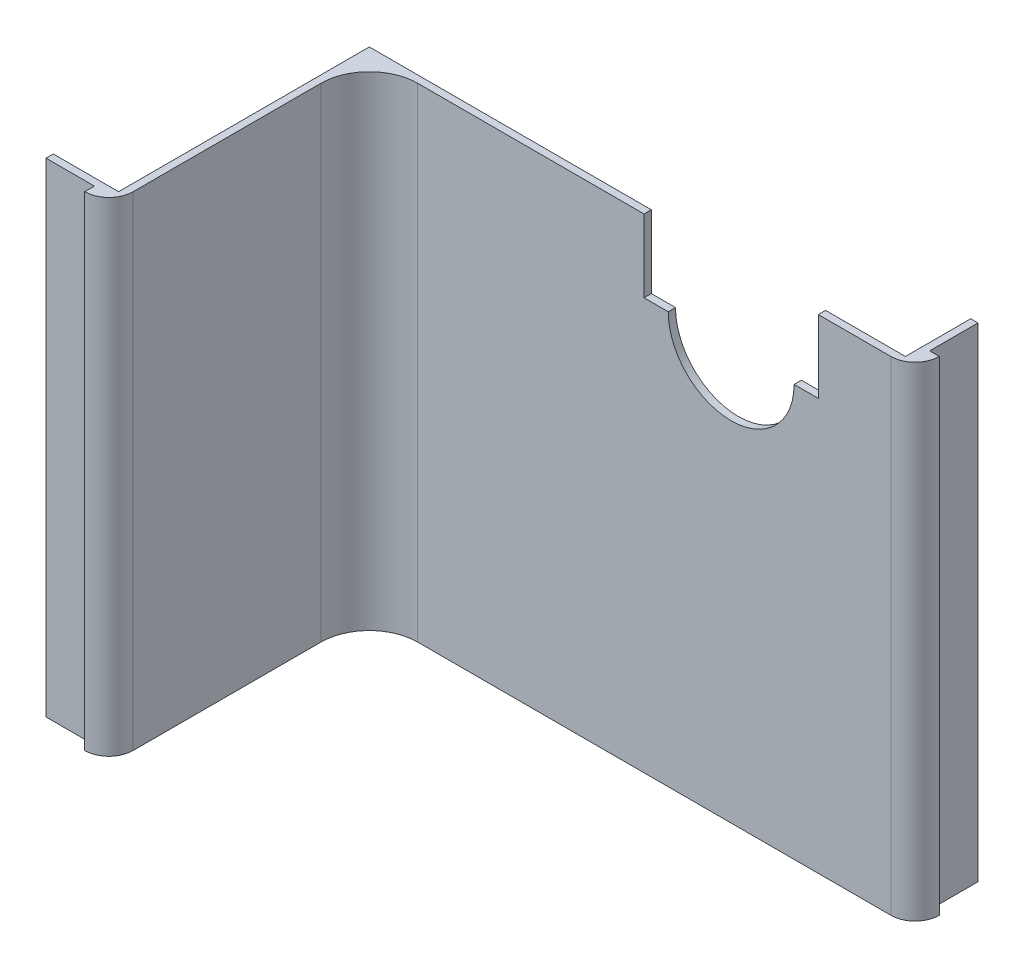
SolidWorks part; units mm, degrees
material "ABS"
ref_plane "Спереди" through (0, 0, 0) normal (0, 0, 1) x (1, 0, 0)
ref_plane "Сверху" through (0, 0, 0) normal (0, 1, 0) x (1, 0, 0)
ref_plane "Справа" through (0, 0, 0) normal (1, 0, 0) x (0, 0, -1)
sketch "Эскиз1" plane through (0, 0, 0) normal (0, 1, 0) x (1, 0, 0)
  line L0 (0, 0) -> (-97.768, 0)
  line L1 (-107.768, -10) -> (-107.768, -48.8)
  line L2 (-112.768, -53.8) -> (-112.768, -51.8)
  line L3 (-112.768, -51.8) -> (-122.768, -51.8)
  line L4 (5, 5) -> (3, 5)
  line L5 (3, 5) -> (3, 15)
  line L6 (3, 15) -> (1.5, 15)
  line L7 (0, 0) -> (0, 1.5) construction
  line L8 (1.5, 15) -> (1.5, 1.5)
  line L9 (-107.768, -48.8) -> (-109.268, -48.8) construction
  line L10 (-122.768, -51.8) -> (-122.768, -50.3)
  line L11 (-122.768, -50.3) -> (-109.268, -50.3)
  line L12 (-109.268, -50.3) -> (-109.268, 1.5)
  line L13 (-109.268, 1.5) -> (1.5, 1.5)
  arc A0 (-97.768, 0) -> (-107.768, -10) centre (-97.768, -10) ccw
  arc A1 (-107.768, -48.8) -> (-112.768, -53.8) centre (-112.768, -48.8) cw
  arc A2 (0, 0) -> (5, 5) centre (0, 5) ccw
  dimension "D1" = 97.768
  dimension "D2" = 5
  dimension "D6" = 10
  dimension "D9" = 5
  dimension "D3" = 2
  dimension "D4" = 1.5
  dimension "D5" = 1.5
  dimension "D7" = 1.5
  dimension "D8" = 38.8
  dimension "D10" = 2
  dimension "D11" = 1.5
  dimension "D12" = 10
  dimension "D13" = 10
extrude "Бобышка-Вытянуть1" add sketch "Эскиз1" along normal blind 100
sketch "Эскиз4" plane through (0, 0, 0) normal (0, 0, 1) x (1, 0, 0)
  line L8 (-51, 85) -> (-15, 85) construction
  line L11 (5, 50) -> (-55.9199, 50) construction
  line L12 (5, 100) -> (-15, 100) construction
  line L13 (-15, 85) -> (-20, 85)
  line L14 (-15, 100) -> (-15, 85)
  line L15 (-51, 85) -> (-46, 85)
  line L16 (-51, 100) -> (-51, 85)
  line L17 (-15, 100) -> (-51, 100)
  arc A1 (-20, 85) -> (-46, 85) centre (-33, 85) cw
  point P12 (0, 0)
extrude "Вырез-Вытянуть1" cut sketch "Эскиз4" against normal through all
